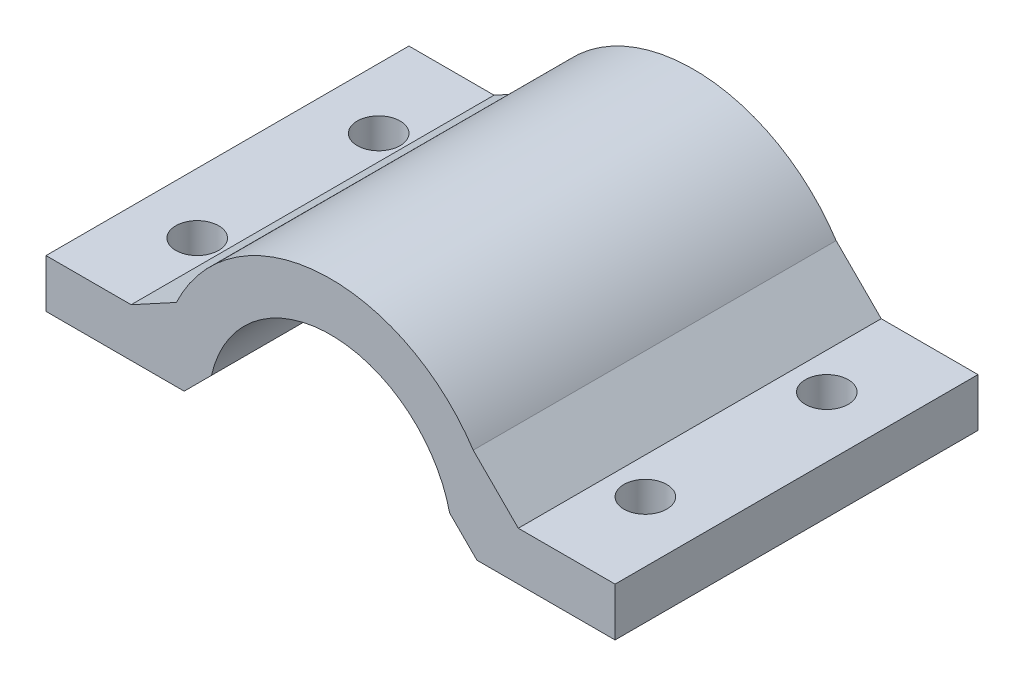
SolidWorks part; units mm, degrees
ref_plane "Front Plane" through (0, 0, 0) normal (0, 0, 1) x (1, 0, 0)
ref_plane "Top Plane" through (0, 0, 0) normal (0, 1, 0) x (1, 0, 0)
ref_plane "Right Plane" through (0, 0, 0) normal (1, 0, 0) x (0, 0, -1)
sketch "Sketch1" plane through (0, 0, 0) normal (0, 0, 1) x (1, 0, 0)
  line L0 (0, 0) -> (17.0443, 0)
  line L1 (0, 0) -> (0, 5.08)
  line L2 (0, 5.08) -> (12.7, 5.08)
  line L3 (29.8713, 0) -> (29.8713, 17.907) construction
  line L4 (59.7426, 0) -> (59.7426, 5.08)
  line L5 (59.7426, 5.08) -> (47.0426, 5.08)
  line L6 (59.7426, 0) -> (42.6983, 0)
  line L7 (29.8713, 0) -> (17.0443, 0)
  circle A0 centre (29.8713, 0) radius 12.827
  circle A1 centre (29.8713, 0) radius 17.907
  dimension "D1" = 25.654
extrude "Boss-Extrude1" add sketch "Sketch1" along normal blind 38.1 contours A1 L2 L1 L0 | A0 L3 A1 L0 | L3 A0 L6 A1 | A1 L6 L4 L5 region at (6.1057, 2.5654, 0) region at (19.9993, 9.872, 0) region at (53.6369, 2.5654, 0) region at (39.7433, 9.872, 0)
sketch3d "3DSketch2"
  line L0 (0, 0, 0) -> (29.7388, 0, 0)
  line L1 (29.8713, 0, 38.1) -> (29.8713, 0, 0) construction
  line L2 (29.8713, 0, 38.1) -> (29.8713, 0, 0) construction
  line L3 (29.7388, 0, 0) -> (29.7388, 0, 19.05)
  line L4 (29.7388, 0, 19.05) -> (29.7388, 38.1, 19.05)
  dimension "D1" = 19.05
sketch "Sketch2" plane through (0, 5.08, 0) normal (0, 1, 0) x (1, 0, 0)
  line L0 (0, -26.0274) -> (29.7388, -19.05)
  line L1 (0, -38.1) -> (0, 0) construction
  line L2 (0, -26.0274) -> (0, -22.6748)
  line L3 (0, -22.6748) -> (59.7426, -8.6579)
  line L4 (59.7426, -38.1) -> (59.7426, 0) construction
  line L5 (0, -26.0274) -> (0, -29.3799)
  line L6 (0, -29.3799) -> (59.7426, -15.363)
  line L7 (0, -29.3799) -> (0, -34.5979)
  line L8 (0, -34.5979) -> (59.7426, -20.5809)
  line L9 (0, -22.6748) -> (0, -17.4569)
  line L10 (0, -17.4569) -> (59.7426, -3.44)
  line L11 (59.7426, -3.44) -> (59.7426, -20.5809)
  line L13 (12.7, 0) -> (12.7, -38.1)
  line L14 (47.0426, 0) -> (47.0426, -38.1)
  line L15 (0, 0) -> (12.7, 0)
  line L16 (0, 0) -> (0, -19.05)
  line L17 (0, -9.525) -> (6.35, -9.525)
  line L18 (6.35, -9.525) -> (6.35, 0)
  line L19 (6.35, -6.7783) -> (7.6405, -7.6819)
  line L20 (6.35, -6.7783) -> (5.0595, -7.6819)
  line L21 (59.7426, -19.05) -> (0, -19.05) construction
  line L22 (6.35, -28.575) -> (6.35, -25.8283)
  line L23 (6.35, -25.8283) -> (7.6405, -26.7319)
  line L24 (6.35, -25.8283) -> (5.0595, -26.7319)
  line L25 (29.8713, 0) -> (29.8713, -38.1) construction
  line L26 (47.0426, 0) -> (12.7, 0) construction
  line L27 (12.7, -38.1) -> (47.0426, -38.1) construction
  line L28 (53.3926, -25.8283) -> (54.6832, -26.7319)
  line L29 (53.3926, -25.8283) -> (52.1021, -26.7319)
  line L30 (53.3926, -6.7783) -> (54.6832, -7.6819)
  line L31 (53.3926, -6.7783) -> (52.1021, -7.6819)
  line L32 (42.9272, -0.4976) -> (42.5468, -0.5868) construction
  circle A0 centre (6.35, -9.525) radius 2.25
  circle A1 centre (6.35, -28.575) radius 2.25
  circle A2 centre (53.3926, -28.575) radius 2.25
  circle A3 centre (53.3926, -9.525) radius 2.25
  line M13 (12.7, -38.1) -> (12.7, 0)
  dimension "D4" = 4.5
  dimension "D3" = 55
  dimension "D5" = 55
extrude "Boss-Extrude2" [suppressed] add sketch "Sketch2" along normal blind 35.56 from surface contours L14 L6 L8 M13 | L14 L10 L3 M13
sketch "Sketch3" [suppressed] plane through (3.8821, 0, 16.5461) normal (-0.2284, 0, -0.9736) x (-0.9736, 0, 0.2284)
  line L0 (-24.6012, 38.1) -> (-24.6012, 42.131)
  line L1 (-24.6012, 42.131) -> (-22.7073, 40.8048)
  line L2 (-24.6012, 42.131) -> (-26.4952, 40.8048)
  circle A0 centre (-24.6012, 38.1) radius 3.302
  dimension "D2" = 55
extrude "Cut-Extrude1" [suppressed] cut sketch "Sketch3" against normal through all contours A0 | A0 L0 L2 | A0 L1 L0
chamfer "Chamfer1" distance 2.54 angle 45 4 edges at (12.7, 5.08, 19.05) (47.0426, 5.08, 19.05) (17.0443, 0, 19.05) (42.6983, 0, 19.05) first distance on face at (29.8713, 11.4935, 19.05) first distance on face at (53.3926, 5.08, 19.05) first distance on face at (8.5222, 0, 19.05) first distance on face at (29.8713, 6.4135, 19.05)
chamfer "Chamfer2" [suppressed] distance 2.54 angle 45
extrude "Cut-Extrude2" cut sketch "Sketch2<3>" against normal through all contours A2 | A3 L3 | A3 L3 | A1 L6 | A1 L6 L22 | A1 L22 L6 | A0 L18 L17 | L18 A0 L17 region at (5.3746, 5.08, 27.396) region at (6.4885, 5.08, 29.1654) region at (7.0839, 5.08, 27.1161) region at (53.2471, 5.08, 8.9049) region at (53.6873, 5.08, 10.7809) region at (5.3951, 5.08, 8.5701) region at (6.6683, 5.08, 9.8433) region at (53.3926, 5.08, 28.575)
sketch "Sketch2<3>" plane through (0, 5.08, 0) normal (0, 1, 0) x (1, 0, 0) same geometry as "Sketch2"
equation "\"wall thickness\"= .2"
equation "\"D3@Sketch1\"=\"wall thickness\""
equation "\"D2@Sketch1\"=\"wall thickness\""
equation "\"length extrude\"= 1.5"
equation "\"D1@Boss-Extrude1\"=\"length extrude\""
equation "\"D1@3DSketch2\"=\"length extrude\"/2"
equation "\"Teardrop angle\"= 55"
equation "\"D3@Sketch2\"=\"Teardrop angle\""
equation "\"D5@Sketch2\"=\"Teardrop angle\""
equation "\"D2@Sketch3\"=\"Teardrop angle\""
equation "\"D2@Sketch2\"=\"wall thickness\""
